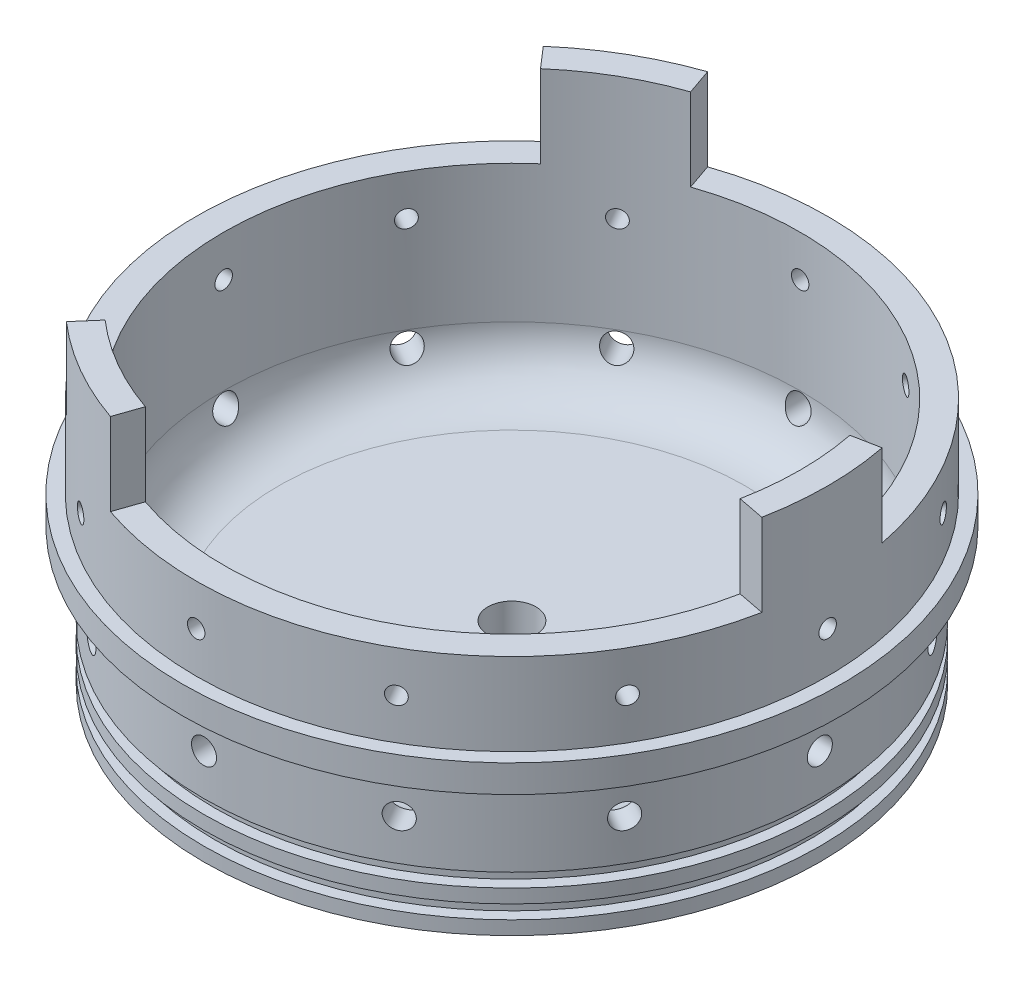
SolidWorks part; units mm, degrees
material "2024-T4"
ref_plane "Front Plane" through (0, 0, 0) normal (0, 0, 1) x (1, 0, 0)
ref_plane "Top Plane" through (0, 0, 0) normal (0, 1, 0) x (1, 0, 0)
ref_plane "Right Plane" through (0, 0, 0) normal (1, 0, 0) x (0, 0, -1)
sketch "Sketch1" plane through (0, 0, 0) normal (0, 1, 0) x (1, 0, 0)
  circle A0 centre (0, 0) radius 76.2
  dimension "D1" = 152.4
extrude "Center Ring(TotOD&Thk)" add sketch "Sketch1" along normal blind 6.35
sketch "Sketch2" plane through (0, 6.35, 0) normal (0, 1, 0) x (1, 0, 0)
  circle A0 centre (0, 0) radius 73.025
  dimension "D1" = 146.05
extrude "Top Ring(AcrylicID&Hgt)" add sketch "Sketch2" along normal blind 38.1
sketch "Sketch3" plane through (0, 0, 0) normal (0, -1, 0) x (1, 0, 0)
  circle A0 centre (0, 0) radius 71.247
  dimension "D1" = 142.494
extrude "Lower Ring(TankID&Depth)" add sketch "Sketch3" along normal blind 31.75
sketch "Sketch4" plane through (0, 44.45, 0) normal (0, 1, 0) x (1, 0, 0)
  circle A0 centre (0, 0) radius 66.675
  circle A1 centre (0, 0) radius 73.025 construction
  circle A2 centre (0, 0) radius 73.025
  dimension "D1" = 133.35
extrude "Bulkhead Hollow(UpperWall&BlkhdThk" cut sketch "Sketch4" against normal offset from surface (63.5 mm away) 12.7 contours A0 up to face at (0, -31.75, -71.247)
sketch "Sketch5" plane through (0, 0, 0) normal (0, 0, 1) x (1, 0, 0)
  line L0 (-71.247, 0) -> (-71.247, -31.75) construction
  line L1 (-71.247, 0) -> (-71.247, -31.75)
  line L2 (-71.247, -28.575) -> (-68.707, -28.575)
  line L3 (-68.707, -28.575) -> (-68.707, -25.4)
  line L4 (-68.707, -25.4) -> (-71.247, -25.4)
  line L5 (-71.247, -22.225) -> (-68.707, -22.225)
  line L6 (-68.707, -22.225) -> (-68.707, -19.05)
  line L7 (-68.707, -19.05) -> (-71.247, -19.05)
  line L8 (-71.247, -31.75) -> (71.247, -31.75) construction
  line L9 (0, 0) -> (0, -31.75) construction
  dimension "D1" = 2.54
  dimension "D2" = 3.175
  dimension "D3" = 3.175
  dimension "D4" = 3.175
  dimension "D5" = 3.175
revolve "O-Ring Channel" cut sketch "Sketch5" angle 360 about L9 region at (-69.977, -20.6375, 0) region at (-69.977, -26.9875, 0)
sketch "Sketch8" plane through (0, 0, 0) normal (0, 0, 1) x (1, 0, 0)
  circle A0 centre (0, -9.525) radius 2.8956
  dimension "D1" = 5.7912
  dimension "D2" = 9.525
extrude "Lower Bolt Hole (DrillDia&Dist)" cut sketch "Sketch8" along normal through all
pattern_circular "Lower Bolt Hole Ammount" count 12 over 360 about axis through (0, -31.75, 0) along (0, 1, 0) of "Lower Bolt Hole (DrillDia&Dist)" reverse direction yes
sketch "Sketch9" plane through (0, 0, 0) normal (0, 0, 1) x (1, 0, 0)
  line L0 (76.2, 6.35) -> (-76.2, 6.35) construction
  line L1 (76.2, 6.35) -> (-76.2, 6.35)
  circle A0 centre (0, 15.875) radius 2.0193
  dimension "D1" = 4.0386
  dimension "D2" = 9.525
extrude "Upper Bolt Hole (DrillDia&Dist)" cut sketch "Sketch9" against normal through all contours A0 region at (0, 15.875, 0)
pattern_circular "CirPattern1" count 12 over 360 about axis through (0, 44.45, 0) along (0, -1, 0) of "Upper Bolt Hole (DrillDia&Dist)"
fillet "Smoothing" radius 12.7 1 edges at (0, -19.05, -66.675)
sketch "Sketch10" plane through (0, 44.45, 0) normal (0, 1, 0) x (1, 0, 0)
  line L0 (65.4543, 12.7) -> (71.688, 13.9095)
  line L1 (65.4543, -12.7) -> (71.688, -13.9095)
  line L2 (-21.7286, -63.0351) -> (-23.798, -69.0384)
  line L3 (-43.7257, -50.3351) -> (-47.89, -55.1289)
  line L4 (-43.7257, 50.3351) -> (-47.89, 55.1289)
  line L5 (-21.7286, 63.0351) -> (-23.798, 69.0384)
  circle A0 centre (0, 0) radius 66.675 construction
  circle A1 centre (0, 0) radius 73.025
  circle A2 centre (0, 0) radius 73.025
  circle A3 centre (0, 0) radius 66.675
  point P20 (0, 0)
  circle M5 centre (0, 0) radius 66.675
  circle M6 centre (0, 0) radius 73.025
  dimension "D2" = 25.4
  dimension "D3" = 12.7
extrude "Cut-Extrude1" cut sketch "Sketch10" against normal blind 19.05 contours L5 L0 M5 M6 | L4 L3 M5 M6 | L2 L1 M5 M6 region at (33.9022, 44.45, -58.7204) region at (68.356, 44.45, 14.4135) region at (-67.8158, 44.45, 0)
sketch "Sketch11" plane through (0, -19.05, 0) normal (0, 1, 0) x (1, 0, 0)
  circle A0 centre (0, 0) radius 5.5562
  dimension "D1" = 11.1125
extrude "1/4NPTHole" cut sketch "Sketch11" against normal through all
equation "\"D4@Sketch5\"=\"D2@Sketch5\""
equation "\"D5@Sketch5\"=\"D3@Sketch5\""
equation "\"D3@Sketch10\"=\"D2@Sketch10\"/2"
